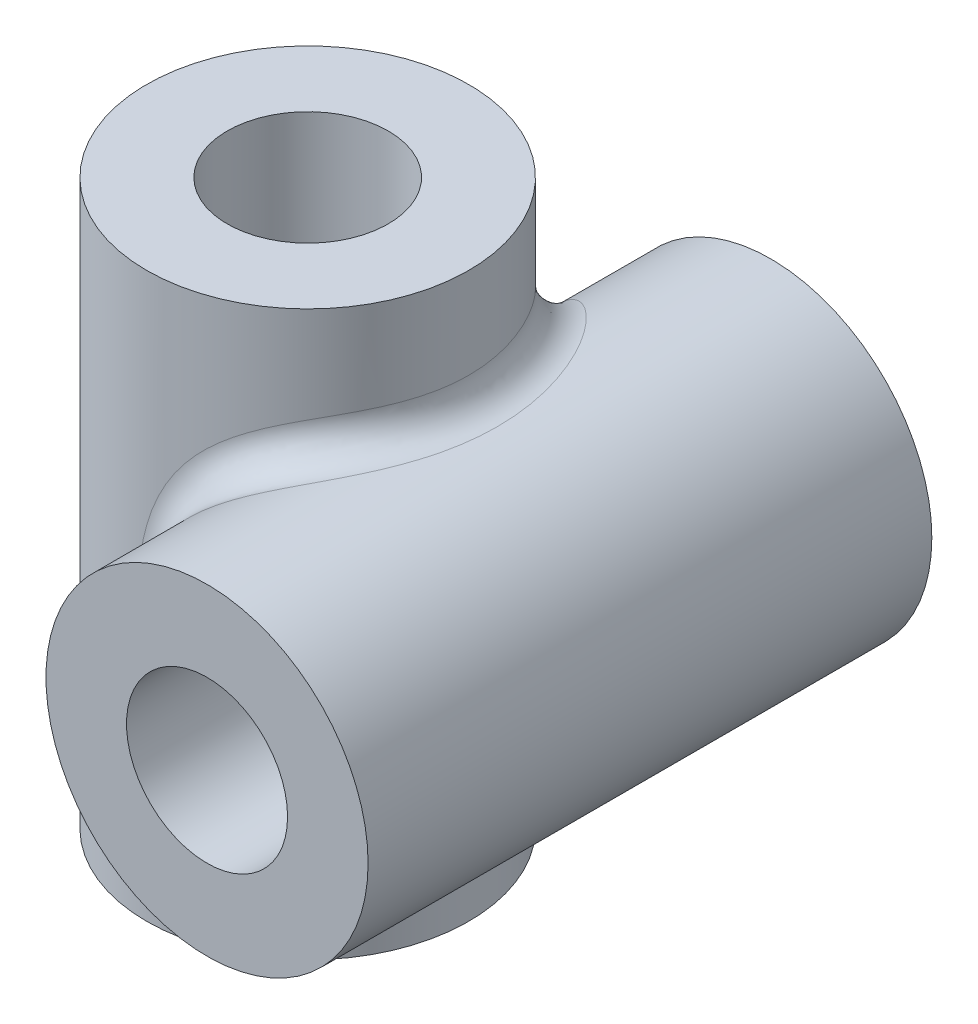
SolidWorks part; units mm, degrees
material "Brass"
ref_plane "Front Plane" through (0, 0, 0) normal (0, 0, 1) x (1, 0, 0)
ref_plane "Top Plane" through (0, 0, 0) normal (0, 1, 0) x (1, 0, 0)
ref_plane "Right Plane" through (0, 0, 0) normal (1, 0, 0) x (0, 0, -1)
sketch "Sketch1" plane through (0, 0, 0) normal (0, 1, 0) x (1, 0, 0)
  circle A0 centre (0, 0) radius 16
  dimension "D1" = 32
extrude "Boss-Extrude1" add sketch "Sketch1" along normal blind 56
sketch "Sketch2" plane through (0, 0, 0) normal (0, 0, 1) x (1, 0, 0)
  line L0 (16, 56) -> (-16, 56) construction
  circle A0 centre (18, 28) radius 16
  point P5 (0, 0)
  dimension "D3" = 32
  dimension "D1" = 18
  dimension "D2" = 28
extrude "Boss-Extrude2" add sketch "Sketch2" along normal mid plane 56
sketch "Sketch3" plane through (0, 0, 0) normal (0, -1, 0) x (1, 0, 0)
  circle A0 centre (0, 0) radius 8
  dimension "D1" = 16
extrude "Cut-Extrude1" cut sketch "Sketch3" against normal through all
sketch "Sketch4" plane through (0, 0, 28) normal (0, 0, 1) x (1, 0, 0)
  circle A0 centre (18, 28) radius 8
  dimension "D1" = 16
extrude "Cut-Extrude2" cut sketch "Sketch4" against normal through all
fillet "Fillet1" radius 3 1 edges at (2.5461, 32.1446, -15.7961)
